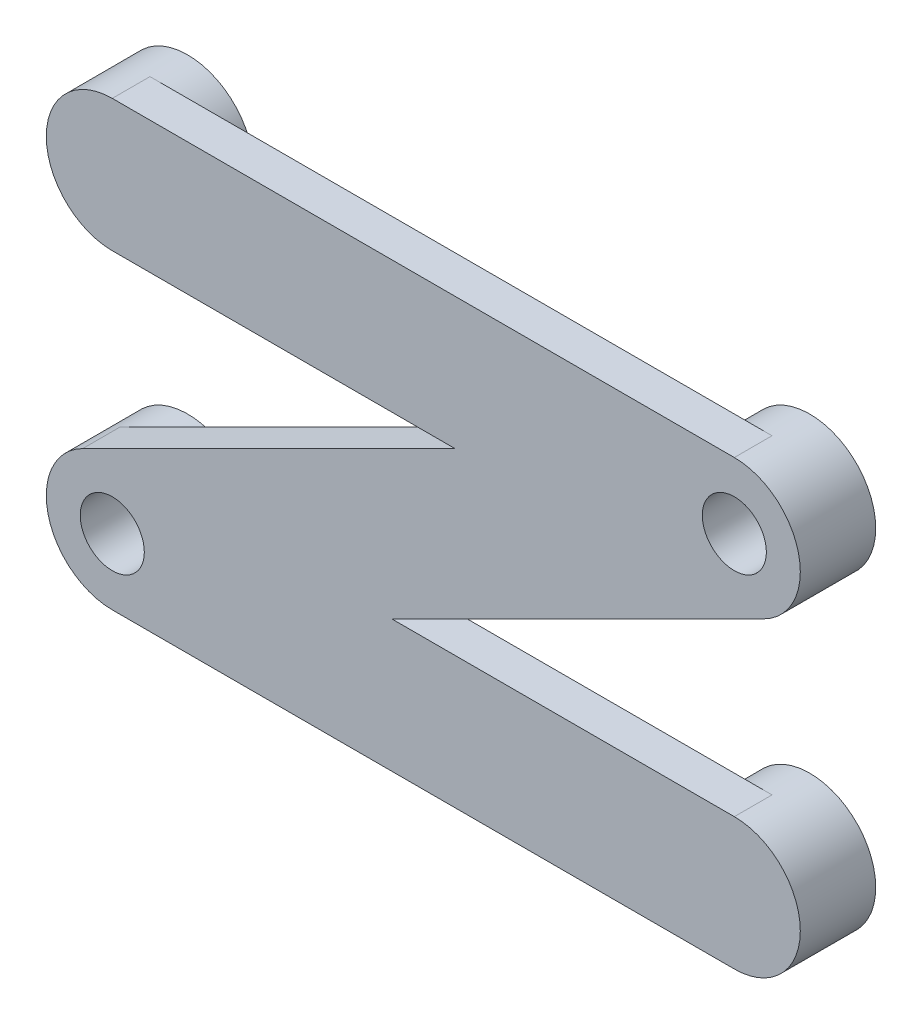
SolidWorks part; units mm, degrees
ref_plane "Спереди" through (0, 0, 0) normal (0, 0, 1) x (1, 0, 0)
ref_plane "Сверху" through (0, 0, 0) normal (0, 1, 0) x (1, 0, 0)
ref_plane "Справа" through (0, 0, 0) normal (1, 0, 0) x (0, 0, -1)
sketch "Эскиз1" plane through (0, 0, 0) normal (0, 0, 1) x (1, 0, 0)
  line L0 (-16.5, 11.75) -> (16.5, 11.75)
  line L5 (-16.5, 8.25) -> (16.5, 8.25) construction
  line L6 (-16.5, 8.25) -> (-16.5, -8.25) construction
  line L7 (-16.5, -8.25) -> (16.5, -8.25) construction
  line L8 (16.5, 8.25) -> (16.5, -8.25) construction
  line L9 (-16.5, 8.25) -> (16.5, -8.25) construction
  line L10 (-16.5, -8.25) -> (16.5, 8.25) construction
  line L11 (-16.5, 4.75) -> (1.6738, 4.75)
  line L12 (-1.6738, -4.75) -> (16.5, -4.75)
  line L13 (18.0652, 5.1195) -> (-1.6738, -4.75)
  line L14 (-16.5, -11.75) -> (16.5, -11.75)
  line L15 (1.6738, 4.75) -> (-18.0652, -5.1195)
  circle A0 centre (16.5, 8.25) radius 3.5
  circle A1 centre (16.5, -8.25) radius 3.5
  circle A2 centre (-16.5, -8.25) radius 3.5
  circle A3 centre (-16.5, 8.25) radius 3.5
  circle A8 centre (16.5, 8.25) radius 1.7
  circle A9 centre (-16.5, -8.25) radius 1.7
  point P4 (0, 0)
  dimension "D3" = 7
  dimension "D4" = 3.4
  dimension "D1" = 33
  dimension "D2" = 16.5
extrude "Основа" add sketch "Эскиз1" against normal blind 2 contours A3 L11 L15 A2 L14 A1 L12 L13 A0 L0 region at (0, 0, 0)
extrude "Стойки" add sketch "Эскиз1<3>" against normal blind 4 contours A3 | A0 | A1 | A2 region at (-16.5, 8.25, 0) region at (18.9049, 10.6549, 0) region at (-14.712, -5.3569, 0) region at (16.5, -8.25, 0)
sketch "Эскиз1<3>" plane through (0, 0, 0) normal (0, 0, 1) x (1, 0, 0) same geometry as "Эскиз1"
